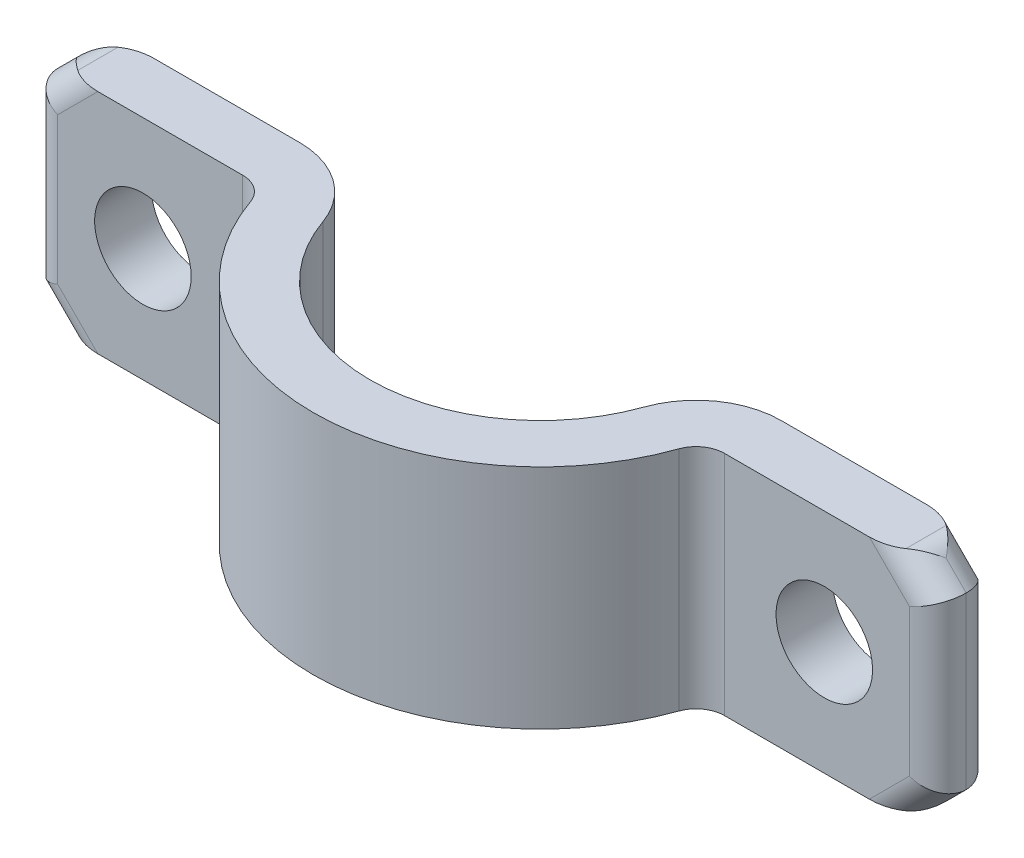
SolidWorks part; units mm, degrees
ref_plane "Front Plane" through (0, 0, 0) normal (0, 0, 1) x (1, 0, 0)
ref_plane "Top Plane" through (0, 0, 0) normal (0, 1, 0) x (1, 0, 0)
ref_plane "Right Plane" through (0, 0, 0) normal (1, 0, 0) x (0, 0, -1)
sketch "Sketch1" plane through (0, 0, 0) normal (0, 1, 0) x (1, 0, 0)
  line L0 (-16, 0) -> (-8.4853, 0)
  line L1 (-16, 0) -> (-16, -2)
  line L2 (-16, -2) -> (-8.4853, -2)
  line L3 (0, -6) -> (0, -8)
  line L4 (0, -55) -> (0, 55) construction
  line L5 (0, -8) -> (-7.5415, -8) construction
  line L8 (-55, 0) -> (55, 0) construction
  arc A0 (-8.4853, 0) -> (-5.6569, -2) centre (-8.4853, -3) cw
  arc A1 (-5.6569, -2) -> (0, -6) centre (0, 0) ccw
  arc A2 (-8.4853, -2) -> (-7.5425, -2.6667) centre (-8.4853, -3) cw
  arc A3 (-7.5425, -2.6667) -> (0, -8) centre (0, 0) ccw
  arc A4 (-7.5425, -2.6667) -> (-8, 0) centre (0, 0) cw construction
  dimension "D4" = 1
  dimension "D1" = 2
  dimension "D2" = 16
  dimension "D3" = 8
extrude "Boss-Extrude1" add sketch "Sketch1" along normal blind 8
sketch "Sketch2" plane through (0, 0, 2) normal (0, 0, 1) x (1, 0, 0)
  line L0 (-12, 8) -> (-12, 0) construction
  line L1 (-16, 8) -> (-8.4853, 8) construction
  line L2 (-16, 0) -> (-8.4853, 0) construction
  line L3 (-16, 4) -> (-8, 4) construction
  line L4 (-16, 8) -> (-16, 0) construction
  circle A0 centre (-12, 4) radius 1.7
  dimension "D1" = 3.4
extrude "Cut-Extrude1" cut sketch "Sketch2" against normal through all
chamfer "Chamfer1" distance 1 angle 45 2 edges at (-16, 0, 1) (-16, 8, 1)
fillet "Fillet1" radius 1 8 edges at (-16, 4, 0) (-16, 4, 2) (-15.5, 0.5, 0) (-15.5, 0.5, 2) (-15.5, 7.5, 0) (-15.5, 7.5, 2) (-15, 8, 1) (-15, 0, 1)
mirror "Mirror1" about plane through (0, 8, 6) normal (-1, 0, 0) of bodies 103 101
equation "\"M3_d\"= 3.4"
equation "\"D1@Sketch2\"=\"M3_d\""
